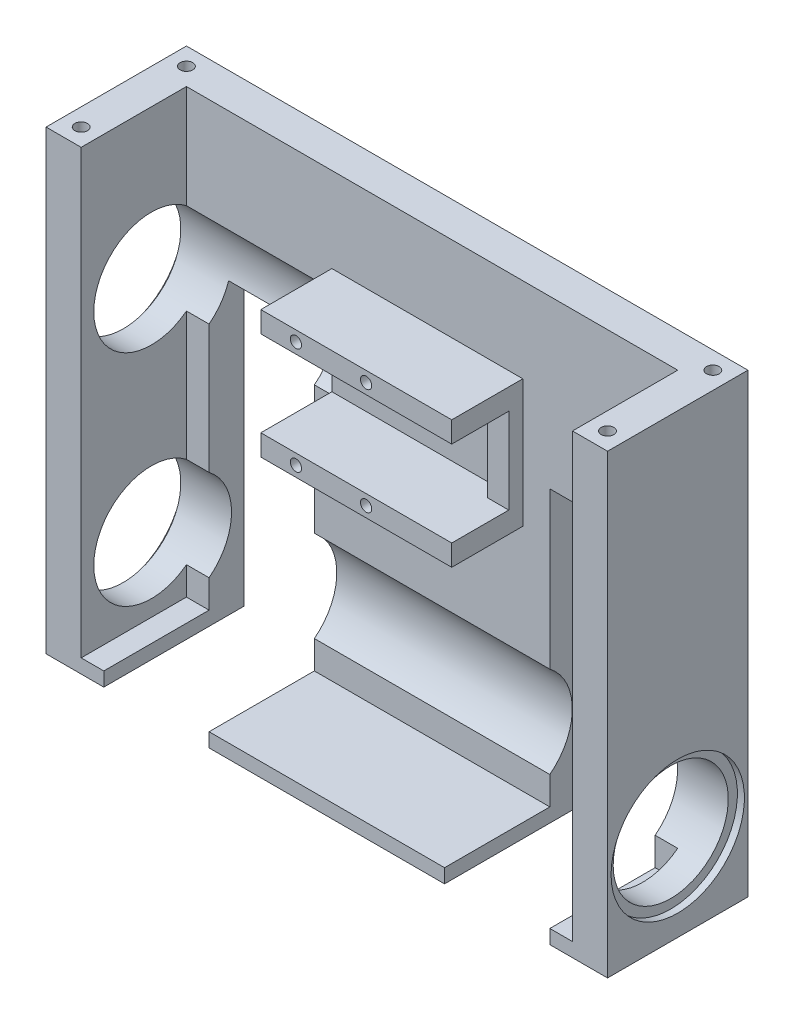
SolidWorks part; units mm, degrees
ref_plane "Front Plane" through (0, 0, 0) normal (0, 0, 1) x (1, 0, 0)
ref_plane "Top Plane" through (0, 0, 0) normal (0, 1, 0) x (1, 0, 0)
ref_plane "Right Plane" through (0, 0, 0) normal (1, 0, 0) x (0, 0, -1)
sketch "Sketch1" plane through (0, 0, 0) normal (0, 0, 1) x (1, 0, 0)
  line L1 (-40, -32.5) -> (40, -32.5)
  line L2 (-40, -32.5) -> (-40, 32.5)
  line L3 (-40, 32.5) -> (40, 32.5)
  line L4 (40, -32.5) -> (40, 32.5)
  line L5 (-40, -32.5) -> (40, 32.5) construction
  line L6 (-40, 32.5) -> (40, -32.5) construction
  point P0 (0, 0)
  dimension "D1" = 80
  dimension "D2" = 65
extrude "Boss-Extrude1" add sketch "Sketch1" along normal blind 20
sketch "Sketch2" plane through (0, 0, 20) normal (0, 0, 1) x (1, 0, 0)
  line L4 (0, 32.5) -> (0, 30.5) construction
  line L7 (40, 32.5) -> (-40, 32.5) construction
  line L8 (0, 30.5) -> (0, -30.5) construction
  line L9 (0, -30.5) -> (0, -32.5) construction
  line L10 (-40, -32.5) -> (40, -32.5) construction
  line L11 (-40, 0) -> (-35, 0) construction
  line L12 (35, -30.5) -> (35, 30.5)
  line L13 (35, 30.5) -> (-35, 30.5)
  line L14 (-35, 30.5) -> (-35, -30.5)
  line L15 (-35, -30.5) -> (35, -30.5)
  line L16 (-40, 32.5) -> (-40, -32.5) construction
  line L17 (-35, 0) -> (35, 0) construction
  line L18 (35, 0) -> (40, 0) construction
  line L19 (40, -32.5) -> (40, 32.5) construction
  dimension "D1" = 5
  dimension "D2" = 2
extrude "Cut-Extrude1" cut sketch "Sketch2" against normal offset from surface (15 mm away) 5 up to face at (0, 0, 0)
sketch "Sketch9" plane through (0, 32.5, 0) normal (0, 1, 0) x (1, 0, 0)
  line L0 (40, -20) -> (-40, -20) construction
  line L1 (-35, -20) -> (35, -20)
  line L2 (-35, -20) -> (-35, -5)
  line L3 (-35, -5) -> (35, -5)
  line L4 (35, -20) -> (35, -5)
  line L5 (-35, -5) -> (35, -5) construction
  line L6 (-35, -5) -> (-35, -20) construction
  line L7 (35, -5) -> (35, -20) construction
extrude "Cut-Extrude7" cut sketch "Sketch9" against normal up to next
sketch "Sketch3" plane through (0, 0, 5) normal (0, 0, 1) x (1, 0, 0)
  line L0 (-14.2764, 20.4) -> (-14.2764, 17.4)
  line L1 (-14.2764, 17.4) -> (9.9236, 17.4)
  line L2 (9.9236, 17.4) -> (9.9236, 5.2)
  line L3 (9.9236, 5.2) -> (-14.2764, 5.2)
  line L4 (-14.2764, 5.2) -> (-14.2764, 2.2)
  line L5 (-14.2764, 2.2) -> (12.9236, 2.2)
  line L6 (12.9236, 2.2) -> (12.9236, 20.4)
  line L7 (12.9236, 20.4) -> (-14.2764, 20.4)
  line L8 (9.9236, 11.3) -> (12.9236, 11.3) construction
  line L9 (9.9236, 17.4) -> (12.9236, 17.4)
  line L10 (9.9236, 5.2) -> (12.9236, 5.2)
  line L11 (8.7629, 11.3) -> (-61.2489, 11.3) construction
  line L12 (-76.2524, -20) -> (48.8109, -20) construction
  point P16 (-53.5366, -20)
  dimension "D1" = 3
  dimension "D2" = 24.2
  dimension "D3" = 12.2
  dimension "D4" = 31.3
  dimension "D5" = 12.5
extrude "Boss-Extrude2" add sketch "Sketch3" along normal blind 10.125 contours L1 L9 L6 L7 L0 | L10 L3 L4 L5 L6 region at (-0.6764, 18.9, 5) region at (-0.6764, 3.7, 5)
extrude "Boss-Extrude3" add sketch "Sketch3<3>" along normal blind 2 contours L2 L8 L6 L9 | L8 L2 L10 L6 region at (11.4236, 11.3, 5)
sketch "Sketch3<3>" plane through (0, 0, 5) normal (0, 0, 1) x (1, 0, 0) same geometry as "Sketch3"
sketch "Sketch4" plane through (0, 0, 15.125) normal (0, 0, 1) x (1, 0, 0)
  line L0 (-14.2764, 18.9) -> (12.9236, 18.9) construction
  line L1 (-14.2764, 20.4) -> (-14.2764, 17.4) construction
  line L2 (12.9236, 17.4) -> (12.9236, 20.4) construction
  line L3 (-14.2764, 3.7) -> (12.9236, 3.7) construction
  line L4 (-14.2764, 5.2) -> (-14.2764, 2.2) construction
  line L5 (12.9236, 2.2) -> (12.9236, 5.2) construction
  point P12 (-9.2764, 18.9)
  point P13 (0.7236, 18.9)
  point P14 (0.7236, 3.7)
  point P15 (0.7236, 3.7)
  point P16 (-9.2764, 3.7)
  point P17 (-0.6171, 3.7375)
  point P18 (0, 0)
  dimension "D1" = 10
  dimension "D2" = 5
hole_wizard "Tap Drill for M2x0.4 Tap1" positions "Sketch5" profile "Sketch6" hole size "M2x0.4" standard "ANSI Metric"
sketch "Sketch5" plane through (0, 0, 15.125) normal (0, 0, 1) x (1, 0, 0)
  point P0 (-9.2764, 18.9)
  point P3 (0.7236, 18.9)
  point P6 (0.7236, 3.7)
  point P9 (0.7236, 3.7)
  point P12 (-9.2764, 3.7)
sketch "Sketch6" plane through (-9.2764, 18.9, 15.125) normal (1, 0, 0) x (0, -1, 0)
  line L0 (0, 0) -> (0, 5.4807)
  line L1 (0, 5.4807) -> (0.8, 5)
  line L2 (0.8, 5) -> (0.8, 0)
  line L5 (0.8, 0) -> (0, 0)
  line L10 (0, 5.4807) -> (-0.8, 5) construction
  line L11 (0, -6.35) -> (0, 107.95) construction
  dimension "Hole Dia." = 1.6
  dimension "Hole Depth" = 5
  dimension "Drill Angle" = 118
sketch "Sketch7" plane through (-40, 0, 0) normal (-1, 0, 0) x (0, 0, 1)
  line L0 (10, -6) -> (10, 39.3037) construction
  line L2 (5, 17.4) -> (5, 5.2) construction
  line L3 (0, 11.3) -> (20, 11.3) construction
  line L4 (0, 32.5) -> (0, -32.5) construction
  line L5 (20, 32.5) -> (20, -32.5) construction
  line L6 (0, -29.6323) -> (25, -29.6323) construction
  circle A0 centre (10, 11.3) radius 8.2
  circle A1 centre (10, 11.3) radius 9.5
  circle A2 centre (10, -20) radius 8.2
  circle A3 centre (10, -20) radius 9.5
  point P6 (5, 11.3)
  point P7 (5, -20)
  point P20 (5, -29.6323)
  dimension "D2" = 16.4
  dimension "D3" = 19
  dimension "D1" = 5
extrude "Cut-Extrude2" cut sketch "Sketch7" against normal up to surface (25.7236 mm away) contours A0 region at (-40, 11.3, 10) up to face at (-14.2764, 18.9, 10.0625)
extrude "Cut-Extrude3" cut sketch "Sketch7<3>" against normal blind 1 contours A1 A0 region at (-40, 11.3, 0.7687)
sketch "Sketch7<3>" plane through (-40, 0, 0) normal (-1, 0, 0) x (0, 0, 1) same geometry as "Sketch7"
extrude "Cut-Extrude4" cut sketch "Sketch7<4>" against normal through all contours A2 region at (-40, -20, 10)
sketch "Sketch7<4>" plane through (-40, 0, 0) normal (-1, 0, 0) x (0, 0, 1) same geometry as "Sketch7"
ref_plane "Plane1" through (0, 0, 0) normal (1, 0, 0) x (0, 0, -1)
extrude "Cut-Extrude5" cut sketch "Sketch7<5>" against normal blind 1 contours A3 A2 region at (-40, -20, 0.7687)
sketch "Sketch7<5>" plane through (-40, 0, 0) normal (-1, 0, 0) x (0, 0, 1) same geometry as "Sketch7"
mirror "Mirror1" about plane through (0, 0, 0) normal (1, 0, 0) of "Cut-Extrude5"
sketch "Sketch8" plane through (0, 0, 0) normal (0, 0, -1) x (-1, 0, 0)
  line L0 (-200008.7629, 11.3) -> (200061.2489, 11.3) construction
  line L1 (29.2764, 1.3) -> (19.2764, 1.3)
  line L2 (29.2764, 1.3) -> (29.2764, 21.3)
  line L3 (29.2764, 21.3) -> (19.2764, 21.3)
  line L4 (19.2764, 1.3) -> (19.2764, 21.3)
  line L5 (29.2764, 1.3) -> (19.2764, 21.3) construction
  line L6 (29.2764, 21.3) -> (19.2764, 1.3) construction
  line L7 (0, 37.5127) -> (0, -50.8434) construction
  line L8 (31.7764, -48.75) -> (16.7764, -48.75)
  line L9 (31.7764, -48.75) -> (31.7764, 8.75)
  line L10 (31.7764, 8.75) -> (16.7764, 8.75)
  line L11 (16.7764, -48.75) -> (16.7764, 8.75)
  line L12 (31.7764, -48.75) -> (16.7764, 8.75) construction
  line L13 (31.7764, 8.75) -> (16.7764, -48.75) construction
  line L14 (-31.7764, -48.75) -> (-16.7764, -48.75)
  line L15 (14.2764, 17.4) -> (14.2764, 5.2) construction
  line L16 (-16.7764, -48.75) -> (-16.7764, 8.75)
  line L17 (200076.2524, -20) -> (-200048.8109, -20) construction
  line L18 (-31.7764, 8.75) -> (-16.7764, 8.75)
  line L19 (-31.7764, -48.75) -> (-31.7764, 8.75)
  line L20 (-24.2764, 8.75) -> (-24.2764, -48.75) construction
  line L21 (24.2764, 8.75) -> (24.2764, -48.75) construction
  point P0 (24.2764, 11.3)
  point P7 (24.2764, -20)
  dimension "D1" = 10
  dimension "D2" = 20
  dimension "D3" = 15
  dimension "D4" = 57.5
  dimension "D5" = 10
extrude "Cut-Extrude6" cut sketch "Sketch8" against normal through all both and the other way through all contours L11 L10 L9 L8 | L16 L18 L19 L14
ref_plane "Plane2" through (24.2764, 0, 0) normal (1, 0, 0) x (0, 0, -1)
ref_plane "Plane3" through (-24.2764, 0, 0) normal (1, 0, 0) x (0, 0, -1)
hole_wizard "Tap Drill for M2x0.4 Tap2" positions "Sketch10" profile "Sketch12" hole size "M2x0.4" standard "ANSI Metric"
sketch "Sketch10" plane through (0, 32.5, 0) normal (0, 1, 0) x (1, 0, 0)
  line L1 (-37.5, -17.5) -> (37.5, -17.5) construction
  line L2 (-37.5, -17.5) -> (-37.5, -2.5) construction
  line L3 (-37.5, -2.5) -> (37.5, -2.5) construction
  line L4 (37.5, -17.5) -> (37.5, -2.5) construction
  line L5 (40, 0) -> (-40, 0) construction
  line L6 (-40, -20) -> (-40, 0) construction
  line L7 (40, -20) -> (40, 0) construction
  line L8 (-35, -20) -> (-40, -20) construction
  point P0 (-37.5, -17.5)
  point P2 (-37.5, -2.5)
  point P4 (37.5, -2.5)
  point P6 (37.5, -17.5)
  point P102 (-38.5338, -2.0779)
  point P103 (0, 0)
  point P104 (-46.9471, -18.8188)
  point P105 (0, 0)
  point P106 (33.8282, 1.4242)
  point P107 (-37.5288, -2.5493)
  point P108 (-37.6725, -17.7445)
  dimension "D1" = 2.5
  dimension "D2" = 2.5
  dimension "D3" = 2.5
  dimension "D4" = 2.5
sketch "Sketch12" plane through (-37.5, 32.5, 17.5) normal (1, 0, 0) x (0, 0, 1)
  line L0 (0, 0) -> (0, 10.5408)
  line L1 (0, 10.5408) -> (0.9, 10)
  line L2 (0.9, 10) -> (0.9, 0)
  line L5 (0.9, 0) -> (0, 0)
  line L10 (0, 10.5408) -> (-0.9, 10) construction
  line L11 (0, -6.35) -> (0, 107.95) construction
  dimension "Hole Dia." = 1.8
  dimension "Hole Depth" = 10
  dimension "Drill Angle" = 118
